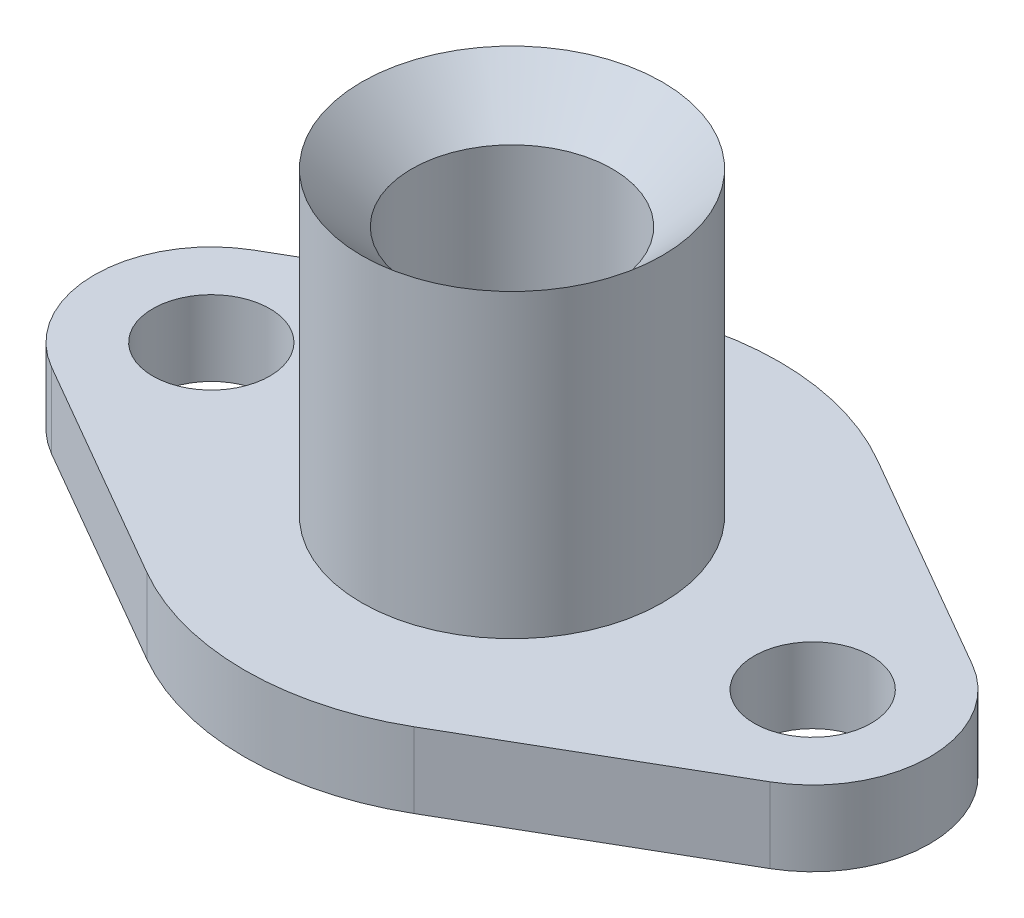
SolidWorks part; units mm, degrees
ref_plane "前基準面" through (0, 0, 0) normal (0, 0, 1) x (1, 0, 0)
ref_plane "上基準面" through (0, 0, 0) normal (0, 1, 0) x (1, 0, 0)
ref_plane "右基準面" through (0, 0, 0) normal (1, 0, 0) x (0, 0, -1)
sketch "草圖1" plane through (0, 0, 0) normal (0, 1, 0) x (1, 0, 0)
  line L0 (0, 0) -> (0, 44.5403) construction
  line L1 (-46.596, 0) -> (46.596, 0) construction
  line L2 (16, 27.7128) -> (43, 12.1244)
  line L3 (16, -27.7128) -> (43, -12.1244)
  line L4 (-16, -27.7128) -> (-43, -12.1244)
  line L5 (-16, 27.7128) -> (-43, 12.1244)
  circle A0 centre (0, 0) radius 12
  circle A1 centre (0, 0) radius 18
  circle A2 centre (0, 0) radius 32
  circle A3 centre (36, 0) radius 7
  arc A4 (43, -12.1244) -> (43, 12.1244) centre (36, 0) ccw
  arc A5 (-43, -12.1244) -> (-43, 12.1244) centre (-36, 0) cw
  circle A6 centre (-36, 0) radius 7
  dimension "D1" = 24
  dimension "D2" = 36
  dimension "D3" = 64
  dimension "D4" = 14
  dimension "D5" = 28
  dimension "D6" = 72
extrude "填料-伸長1" add sketch "草圖1" along normal blind 9 contours L3 A4 L2 A2 A3 | A2 A6 L5 A5 L4 | A2 A6 A3 A1 region at (25.522, 0, -17.7742) region at (29.1749, 0, -19.3555) region at (-26.793, 0, -18.6594)
extrude "填料-伸長2" add sketch "草圖1<3>" along normal blind 45 contours A1 A0 region at (-17.4909, 0, 0)
sketch "草圖1<3>" plane through (0, 0, 0) normal (0, 1, 0) x (1, 0, 0) same geometry as "草圖1"
chamfer "導角1" distance 6 angle 45 2 edges at (0, 0, 12) (0, 45, 12)
